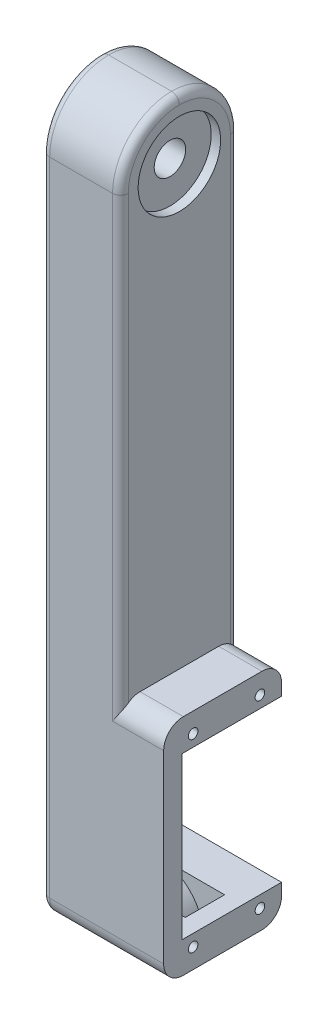
SolidWorks part; units mm, degrees
material "ABS"
ref_plane "Front" through (0, 0, 0) normal (0, 0, 1) x (1, 0, 0)
ref_plane "Top" through (0, 0, 0) normal (0, 1, 0) x (1, 0, 0)
ref_plane "Right" through (0, 0, 0) normal (1, 0, 0) x (0, 0, -1)
sketch "Sketch1" plane through (0, 0, 0) normal (0, 1, 0) x (1, 0, 0)
  line L1 (-10, -15) -> (10, -15)
  line L2 (-10, -15) -> (-10, 15)
  line L3 (-10, 15) -> (10, 15)
  line L4 (10, -15) -> (10, 15)
  point P4 (0, -15)
  point P6 (-10, 0)
  dimension "D1" = 30
  dimension "D2" = 20
extrude "Boss-Extrude1" add sketch "Sketch1" along normal blind 183.3
sketch "Sketch13" plane through (10, 0, 0) normal (-1, 0, 0) x (0, 0, 1)
  line L0 (15, 183.3) -> (15, 0) construction
  line L1 (-15, 0) -> (15, 0)
  line L2 (-15, 0) -> (-15, 57)
  line L3 (-15, 57) -> (15, 57)
  line L4 (15, 0) -> (15, 57)
  dimension "D1" = 57
extrude "Boss-Extrude2" add sketch "Sketch13" against normal blind 11
sketch "Sketch3" plane through (21, 0, 0) normal (1, 0, 0) x (0, 0, -1)
  line L0 (-15, 0) -> (15, 0) construction
  line L1 (-10.3, 8) -> (10.3, 8)
  line L2 (-10.3, 8) -> (-10.3, 49)
  line L3 (-10.3, 49) -> (10.3, 49)
  line L4 (10.3, 8) -> (10.3, 49)
  point P4 (0, 8)
  point P7 (0, 0)
  dimension "D1" = 20.6
  dimension "D2" = 41
  dimension "D3" = 8
extrude "Cut-Extrude1" cut sketch "Sketch3" against normal blind 40
sketch "Sketch11" plane through (10, 0, 0) normal (-1, 0, 0) x (0, 0, 1)
  line L0 (0, 183.3) -> (0, 168.3) construction
  line L1 (-15, 183.3) -> (15, 183.3) construction
  line L2 (0, 168.3) -> (15, 168.3) construction
  line L3 (15, 183.3) -> (15, 0) construction
  circle A0 centre (0, 168.3) radius 10.5
  dimension "D1" = 21
extrude "Cut-Extrude4" cut sketch "Sketch11" along normal blind 2.4
sketch "Sketch12" plane through (7.6, 0, 0) normal (1, 0, 0) x (0, 0, -1)
  circle A0 centre (0, 168.3) radius 4
  dimension "D1" = 8
extrude "Cut-Extrude5" cut sketch "Sketch12" against normal through all
sketch "Sketch14" plane through (0, 0, -15) normal (0, 0, -1) x (-1, 0, 0)
  line L1 (10, 8) -> (-21, 8)
  line L2 (10, 8) -> (10, 49)
  line L3 (10, 49) -> (-21, 49)
  line L4 (-21, 8) -> (-21, 49)
  line L5 (-21, 57) -> (-21, 0) construction
  line L6 (10, 183.3) -> (10, 0) construction
  line L7 (10, 8) -> (-21, 8) construction
  line L8 (10, 49) -> (-21, 49) construction
extrude "Cut-Extrude6" cut sketch "Sketch14" against normal up to surface (25.3 mm away) up to face at (5.5, 28.5, 10.3)
hole_wizard "#2 Clearance Hole2" positions "Sketch16" profile "Sketch17" hole size "#2" standard "ANSI Inch"
sketch "Sketch16" plane through (21, 0, 0) normal (1, 0, 0) x (0, 0, -1)
  line L0 (-7.5, 5) -> (9.5, 5) construction
  line L1 (9.5, 5) -> (9.5, 52) construction
  line L2 (9.5, 52) -> (-7.5, 52) construction
  line L3 (-7.5, 52) -> (-7.5, 5) construction
  line L5 (-10.3, 49) -> (-10.3, 8) construction
  line L8 (-15, 0) -> (-15, 57) construction
  point P0 (-7.5, 5)
  point P2 (9.5, 5)
  point P4 (-7.5, 52)
  point P6 (9.5, 52)
  point P20 (-10.3, 28.5)
  point P21 (9.5, 28.5)
  dimension "D1" = 47
  dimension "D2" = 17
  dimension "D3" = 7.5
sketch "Sketch17" plane through (21, 5, 7.5) normal (0, 1, 0) x (0, 0, -1)
  line L0 (0, 0) -> (0, 7.0826)
  line L1 (0, 7.0826) -> (1.2192, 6.35)
  line L2 (1.2192, 6.35) -> (1.2192, 0)
  line L5 (1.2192, 0) -> (0, 0)
  line L10 (0, 7.0826) -> (-1.2192, 6.35) construction
  line L11 (0, -6.35) -> (0, 107.95) construction
  dimension "Hole Dia." = 2.4384
  dimension "Hole Depth" = 6.35
  dimension "Drill Angle" = 118
sketch "Sketch18" plane through (21, 0, 0) normal (1, 0, 0) x (0, 0, -1)
  line L1 (-10.329, 5) -> (-8.9145, 2.55)
  line L2 (-8.9145, 2.55) -> (-6.0855, 2.55)
  line L3 (-6.0855, 2.55) -> (-4.671, 5)
  line L4 (-4.671, 5) -> (-6.0855, 7.45)
  line L5 (-6.0855, 7.45) -> (-8.9145, 7.45)
  line L6 (-8.9145, 7.45) -> (-10.329, 5)
  line L7 (12.329, 5) -> (10.9145, 7.45)
  line L8 (10.9145, 7.45) -> (8.0855, 7.45)
  line L9 (8.0855, 7.45) -> (6.671, 5)
  line L10 (6.671, 5) -> (8.0855, 2.55)
  line L11 (8.0855, 2.55) -> (10.9145, 2.55)
  line L12 (10.9145, 2.55) -> (12.329, 5)
  line L13 (6.671, 52) -> (8.0855, 49.55)
  line L14 (8.0855, 49.55) -> (10.9145, 49.55)
  line L15 (10.9145, 49.55) -> (12.329, 52)
  line L16 (12.329, 52) -> (10.9145, 54.45)
  line L17 (10.9145, 54.45) -> (8.0855, 54.45)
  line L18 (8.0855, 54.45) -> (6.671, 52)
  line L19 (-4.671, 52) -> (-6.0855, 54.45)
  line L20 (-6.0855, 54.45) -> (-8.9145, 54.45)
  line L21 (-8.9145, 54.45) -> (-10.329, 52)
  line L22 (-10.329, 52) -> (-8.9145, 49.55)
  line L23 (-8.9145, 49.55) -> (-6.0855, 49.55)
  line L24 (-6.0855, 49.55) -> (-4.671, 52)
  circle A0 centre (-7.5, 5) radius 2.45 construction
  circle A1 centre (9.5, 5) radius 2.45 construction
  circle A2 centre (9.5, 52) radius 2.45 construction
  circle A3 centre (-7.5, 52) radius 2.45 construction
  dimension "D1" = 4.9
extrude "Cut-Extrude8" cut sketch "Sketch18" against normal blind 1.6 from offset 2 offset against normal yes
fillet "Fillet1" [suppressed] radius 10
fillet "Fillet2" [suppressed] radius 3
hole_wizard "#2 Clearance Hole3" positions "Sketch19" profile "Sketch20" hole size "#2" standard "ANSI Inch"
sketch "Sketch19" plane through (-10, 0, 0) normal (1, 0, 0) x (0, 0, -1)
  line L0 (8.22, 4.1) -> (-3.52, 4.1) construction
  line L1 (-3.52, 4.1) -> (-3.52, 52.9) construction
  line L2 (-3.52, 52.9) -> (8.22, 52.9) construction
  line L3 (8.22, 52.9) -> (8.22, 4.1) construction
  line L5 (-10.3, 8) -> (15, 8) construction
  line L6 (-10.3, 49) -> (-10.3, 8) construction
  point P0 (8.22, 4.1)
  point P2 (-3.52, 4.1)
  point P4 (-3.52, 52.9)
  point P6 (8.22, 52.9)
  point P18 (2.35, 4.1)
  point P21 (2.35, 8)
  point P22 (-3.52, 28.5)
  point P25 (-10.3, 28.5)
  dimension "D1" = 48.8
  dimension "D2" = 11.74
sketch "Sketch20" plane through (-10, 4.1, -8.22) normal (0, 1, 0) x (0, 0, 1)
  line L0 (0, 0) -> (0, 7.0826)
  line L1 (0, 7.0826) -> (1.2192, 6.35)
  line L2 (1.2192, 6.35) -> (1.2192, 0)
  line L5 (1.2192, 0) -> (0, 0)
  line L10 (0, 7.0826) -> (-1.2192, 6.35) construction
  line L11 (0, -6.35) -> (0, 107.95) construction
  dimension "Hole Dia." = 2.4384
  dimension "Hole Depth" = 6.35
  dimension "Drill Angle" = 118
fillet "Fillet3" radius 15 2 edges at (0, 183.3, 15) (0, 183.3, -15)
fillet "Fillet4" radius 5 4 edges at (5.5, 0, 15) (5.5, 0, -15) (15.5, 57, 15) (15.5, 57, -15)
fillet "Fillet5" radius 2 12 edges at (-10, 6.5, -15) (-10, 1.4645, -13.5355) (-10, 0, 0) (-10, 1.4645, 13.5355) (-10, 86.65, 15) (-10, 178.9066, 10.6066) (-10, 178.9066, -10.6066) (10, 110.15, 15) (10, 178.9066, 10.6066) (10, 178.9066, -10.6066) (-10, 108.65, -15) (10, 110.15, -15)
sketch "Sketch21" plane through (0, 0, 0) normal (0, -1, 0) x (1, 0, 0)
  line L0 (-10, -10) -> (-10, 10) construction
  line L1 (10.5, -5) -> (16.5, -5)
  line L2 (10.5, -5) -> (10.5, 5)
  line L3 (10.5, 5) -> (16.5, 5)
  line L4 (16.5, -5) -> (16.5, 5)
  point P4 (10.5, 0)
  point P7 (-10, 0)
  point P8 (13.5, -5)
  dimension "D1" = 10
  dimension "D2" = 6
  dimension "D3" = 23.5
extrude "Cut-Extrude9" cut sketch "Sketch21" against normal up to surface (8 mm away) up to face at (2.7172, 8, -4.5628)
fillet "Fillet6" radius 12 1 edges at (10.5, 8, 0)
fillet "Fillet7" radius 6 1 edges at (13.5, 0, 5)
sketch "Sketch22" plane through (-10, 0, 0) normal (-1, 0, 0) x (0, 0, 1)
  line L0 (10.3, 8) -> (-13, 8) construction
  line L1 (0.691, 52.9) -> (2.1055, 50.45)
  line L2 (2.1055, 50.45) -> (4.9345, 50.45)
  line L3 (4.9345, 50.45) -> (6.349, 52.9)
  line L4 (6.349, 52.9) -> (4.9345, 55.35)
  line L5 (4.9345, 55.35) -> (2.1055, 55.35)
  line L6 (2.1055, 55.35) -> (0.691, 52.9)
  line L7 (-11.049, 52.9) -> (-9.6345, 50.45)
  line L8 (-9.6345, 50.45) -> (-6.8055, 50.45)
  line L9 (-6.8055, 50.45) -> (-5.391, 52.9)
  line L10 (-5.391, 52.9) -> (-6.8055, 55.35)
  line L11 (-6.8055, 55.35) -> (-9.6345, 55.35)
  line L12 (-9.6345, 55.35) -> (-11.049, 52.9)
  line L13 (-5.391, 4.1) -> (-6.8055, 6.55)
  line L14 (-6.8055, 6.55) -> (-9.6345, 6.55)
  line L15 (-9.6345, 6.55) -> (-11.049, 4.1)
  line L16 (-11.049, 4.1) -> (-9.6345, 1.65)
  line L17 (-9.6345, 1.65) -> (-6.8055, 1.65)
  line L18 (-6.8055, 1.65) -> (-5.391, 4.1)
  line L19 (6.349, 4.1) -> (4.9345, 6.55)
  line L20 (4.9345, 6.55) -> (2.1055, 6.55)
  line L21 (2.1055, 6.55) -> (0.691, 4.1)
  line L22 (0.691, 4.1) -> (2.1055, 1.65)
  line L23 (2.1055, 1.65) -> (4.9345, 1.65)
  line L24 (4.9345, 1.65) -> (6.349, 4.1)
  circle A0 centre (3.52, 52.9) radius 2.45 construction
  circle A1 centre (-8.22, 52.9) radius 2.45 construction
  circle A2 centre (-8.22, 4.1) radius 2.45 construction
  circle A3 centre (3.52, 4.1) radius 2.45 construction
  dimension "D1" = 4.9
extrude "Cut-Extrude10" cut sketch "Sketch22" against normal blind 1.9 from offset 2 offset against normal yes
